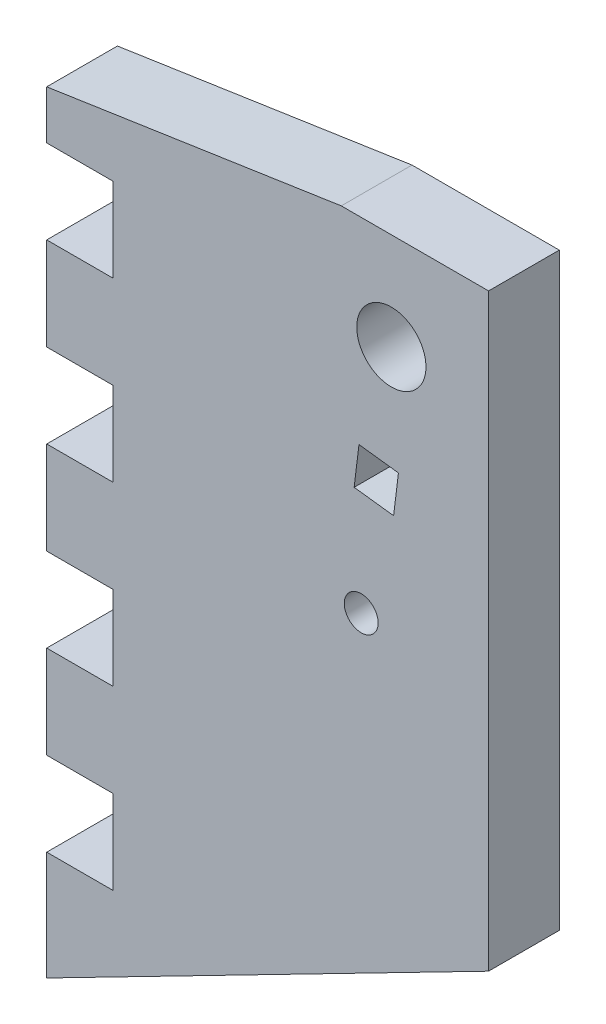
SolidWorks part; units mm, degrees
material "Thornel VCB-20 Carbon Cloth"
ref_plane "Front Plane" through (0, 0, 0) normal (0, 0, 1) x (1, 0, 0)
ref_plane "Top Plane" through (0, 0, 0) normal (0, 1, 0) x (1, 0, 0)
ref_plane "Right Plane" through (0, 0, 0) normal (1, 0, 0) x (0, 0, -1)
sketch "Sketch1" plane through (0, 0, 0) normal (0, 0, 1) x (1, 0, 0)
  line L0 (0, 0) -> (-38.1, 0)
  line L1 (0, 0) -> (0, -50.8)
  line L2 (-38.1, 0) -> (-38.1, -8.001)
  line L3 (-38.1, -8.001) -> (-32.385, -8.001)
  line L4 (-32.385, -8.001) -> (-32.385, -15.24)
  line L5 (-32.385, -15.24) -> (-38.1, -15.24)
  line L6 (-38.1, -45.72) -> (-38.1, -70.358)
  line L7 (-38.1, -15.24) -> (-38.1, -23.241)
  line L8 (-38.1, -23.241) -> (-32.385, -23.241)
  line L9 (-32.385, -23.241) -> (-32.385, -30.48)
  line L10 (-32.385, -30.48) -> (-38.1, -30.48)
  line L11 (-38.1, -30.48) -> (-38.1, -38.481)
  line L12 (-38.1, -38.481) -> (-32.385, -38.481)
  line L13 (-32.385, -38.481) -> (-32.385, -45.72)
  line L14 (-32.385, -45.72) -> (-38.1, -45.72)
  line L15 (-38.1, -70.358) -> (0, -50.8)
  circle A0 centre (-8.382, -8.382) radius 2.9845
  dimension "D9" = 5.969
  dimension "D1" = 38.1
  dimension "D2" = 50.8
  dimension "D3" = 8.001
  dimension "D4" = 7.239
  dimension "D6" = 5.715
  dimension "D8" = 70.358
  dimension "D12" = 8.382
  dimension "D13" = 8.382
  dimension "D7" = 3
extrude "Boss-Extrude1" add sketch "Sketch1" along normal blind 6.096 contours L6 L15 L1 L0 L2 L3 L4 L5 L7 L8 L9 L10 L11 L12 L13 L14 A0 region at (-19.3537, -31.0529, 0)
sketch "Sketch2" plane through (0, 0, 0) normal (0, 0, -1) x (-1, 0, 0)
  line L5 (38.1, 0) -> (12.7, 0)
  line L6 (0, 0) -> (38.1, 0) construction
  line L7 (12.7, 0) -> (38.1, -3.81)
  line L8 (38.1, 0) -> (38.1, -8.001) construction
  line L9 (38.1, -3.81) -> (38.1, 0)
  dimension "D1" = 25.4
  dimension "D2" = 3.81
extrude "Cut-Extrude1" cut sketch "Sketch2" against normal blind 8.636
sketch "Sketch4" plane through (0, 0, 6.096) normal (0, 0, 1) x (1, 0, 0)
  line L0 (-38.1, -45.72) -> (-38.1, -53.721)
  line L1 (-38.1, -45.72) -> (-38.1, -70.358) construction
  line L2 (-38.1, -53.721) -> (-32.385, -53.721)
  line L3 (-32.385, -53.721) -> (-32.385, -60.96)
  line L4 (-32.385, -60.96) -> (-38.1, -60.96)
  line L5 (-38.1, -60.96) -> (-38.1, -53.721)
  line M18 (-38.1, -45.72) -> (-38.1, -70.358)
  dimension "D1" = 7.239
  dimension "D2" = 5.715
  dimension "D3" = 5.715
  dimension "D4" = 8.001
extrude "Cut-Extrude2" cut sketch "Sketch4" against normal through all contours L4 L3 L2 M18 region at (-35.2425, -57.3405, 6.096)
sketch "Sketch5" plane through (0, 0, 0) normal (0, 0, -1) x (-1, 0, 0)
  line L0 (8.382, -8.382) -> (10.9822, -29.559) construction
  line L1 (8.382, -8.382) -> (8.382, -39.2411) construction
  line L2 (7.7714, -17.4777) -> (11.1749, -17.0598)
  line L3 (7.7714, -17.4777) -> (8.1893, -20.8811)
  line L4 (8.1893, -20.8811) -> (11.5928, -20.4633)
  line L5 (11.1749, -17.0598) -> (11.5928, -20.4633)
  circle A0 centre (8.382, -8.382) radius 2.9845 construction
  circle A1 centre (10.9822, -29.559) radius 1.4605
  dimension "D3" = 8.9535
  dimension "D7" = 2.921
  dimension "D1" = 21.336
  dimension "D2" = 7
  dimension "D4" = 1.7145
  dimension "D5" = 3.429
  dimension "D6" = 3.429
  dimension "D8" = 8.9535
extrude "Cut-Extrude4" cut sketch "Sketch5" against normal up to surface (6.096 mm away) up to face at (-5.3975, -8.382, 6.096)
ref_plane "Plane1" through (0, 0, 0) normal (0, 0, -1) x (-1, 0, 0)
